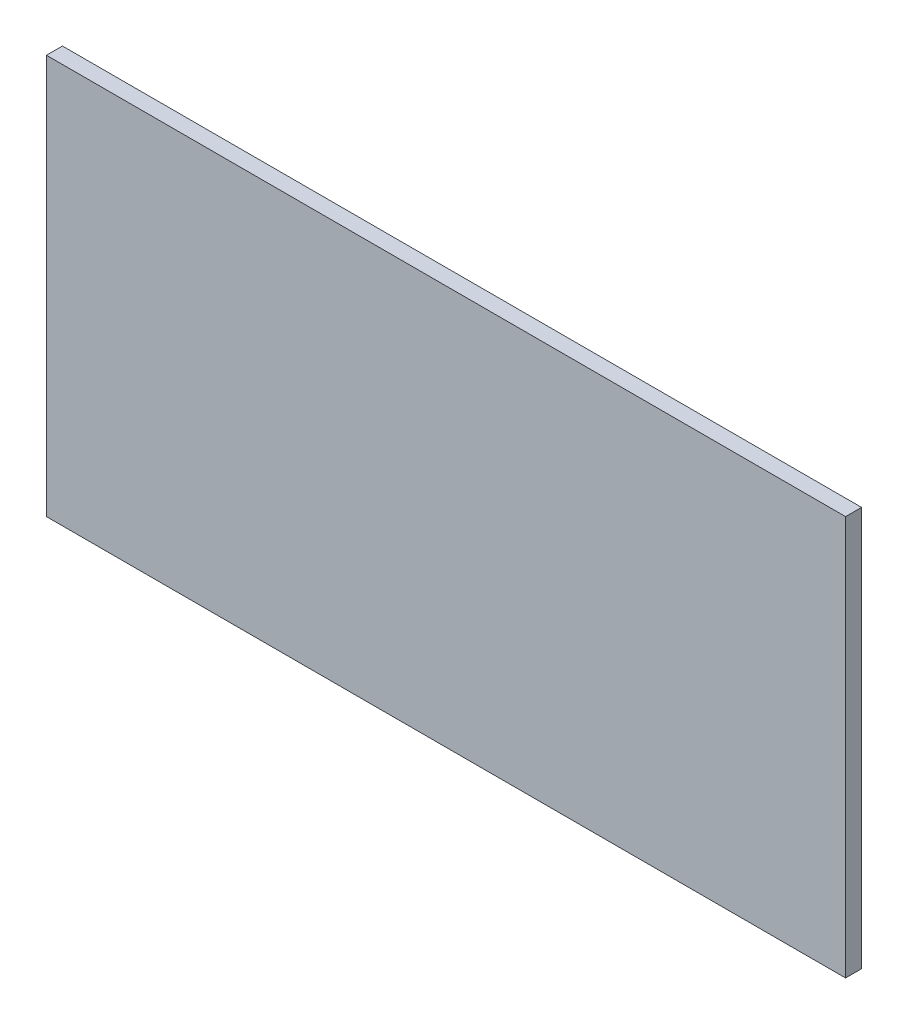
SolidWorks part; units mm, degrees
ref_plane "Спереди" through (0, 0, 0) normal (0, 0, 1) x (1, 0, 0)
ref_plane "Сверху" through (0, 0, 0) normal (0, 1, 0) x (1, 0, 0)
ref_plane "Справа" through (0, 0, 0) normal (1, 0, 0) x (0, 0, -1)
sketch "Эскиз1" plane through (0, 0, 0) normal (0, 0, 1) x (1, 0, 0)
  line L1 (-50, -25) -> (50, -25)
  line L2 (-50, -25) -> (-50, 25)
  line L3 (-50, 25) -> (50, 25)
  line L4 (50, -25) -> (50, 25)
  line L5 (-50, -25) -> (50, 25) construction
  line L6 (-50, 25) -> (50, -25) construction
  point P0 (0, 0)
  dimension "D1" = 100
  dimension "D2" = 50
base flange "Базовая кромка1" sketch "Эскиз1" thickness 2 reverse thickness direction no parameters "D1"=0.7366
sketch "Сгиб-Линии1" [suppressed] plane through (0, 0, 0) normal (0, 1, 0) x (1, 0, 0)
sketch "Граничная рамка1" [suppressed] plane through (0, 0, 0) normal (0, 1, 0) x (1, 0, 0)
sheet metal parameters "Листовой металл1" thickness 2 parameters "D1"=0.7366
flat pattern "Развертка1" [suppressed]
sketch "Сгиб-Линии2" plane through (0, 0, 0) normal (0, 1, 0) x (1, 0, 0)
sketch3d "Граничная рамка2" [suppressed]
  line L0 (50, -25, 0) -> (-50, -25, 0) construction
  line L1 (50, 25, 0) -> (-50, 25, 0) construction
  line L2 (50, -25, 0) -> (50, 25, 0) construction
  line L3 (-50, -25, 0) -> (-50, 25, 0) construction
